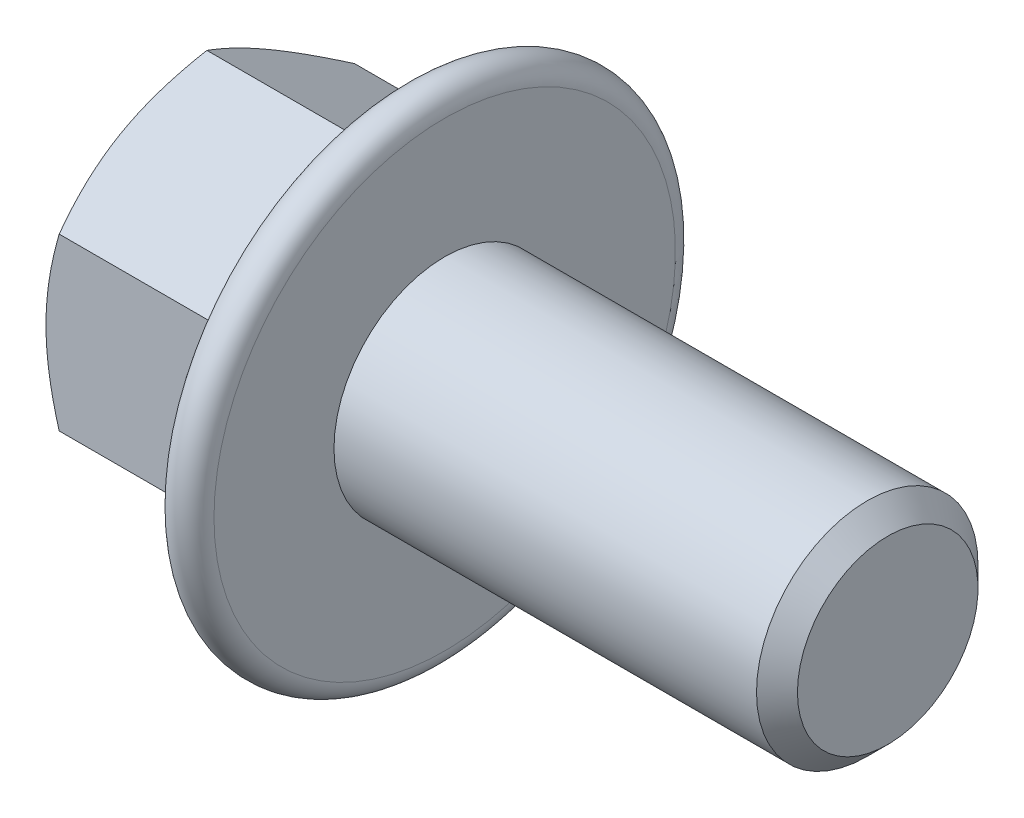
SolidWorks part; units mm, degrees
material "ASTM A36 Steel"
ref_plane "Front Plane" through (0, 0, 0) normal (0, 0, 1) x (1, 0, 0)
ref_plane "Top Plane" through (0, 0, 0) normal (0, 1, 0) x (1, 0, 0)
ref_plane "Right Plane" through (0, 0, 0) normal (1, 0, 0) x (0, 0, -1)
sketch "BaseHeadSke" plane through (0, 0, 0) normal (1, 0, 0) x (0, 0, -1)
  line L1 (0, 4.6188) -> (-4, 2.3094)
  line L2 (-4, 2.3094) -> (-4, -2.3094)
  line L3 (-4, -2.3094) -> (0, -4.6188)
  line L4 (0, -4.6188) -> (4, -2.3094)
  line L5 (4, -2.3094) -> (4, 2.3094)
  line L6 (4, 2.3094) -> (0, 4.6188)
  circle A0 centre (0, 0) radius 4 construction
  dimension "Width_flats" = 8
extrude "BaseHead" add sketch "BaseHeadSke" along normal blind 6.8
sketch "HeadChamferSke" plane through (0, 0, 0) normal (0, 0, 1) x (1, 0, 0)
  line L0 (0, 0) -> (28.0814, 0) construction
  line L1 (0, 2.3094) -> (0, -2.3094) construction
  line L2 (0, 4.6188) -> (0, 4)
  line L3 (0, 4) -> (0.3573, 4.6188)
  line L4 (0.3573, 4.6188) -> (0, 4.6188)
  line L7 (6.8, 4.6188) -> (0, 4.6188) construction
  dimension "Angle_Chamfer_Head" = 30
revolve "HeadChamfer" cut sketch "HeadChamferSke" angle 360 about L0
sketch "BodySke" plane through (0, 0, 0) normal (0, 0, 1) x (1, 0, 0)
  line L0 (0, 0) -> (117.0647, 0) construction
  line L1 (0, 0) -> (0, 3)
  line L2 (0, 3.4641) -> (0, 0) construction
  line L3 (0, 3) -> (18.2455, 3)
  line L4 (18.2455, 3) -> (18.8, 2.4455)
  line L5 (18.8, 2.4455) -> (18.8, 0)
  line L6 (18.8, 0) -> (0, 0)
  line L7 (6.8, 2.3094) -> (6.8, -2.3094) construction
  line L8 (7.8, 0) -> (7.8, 14.6766) construction
  line L9 (6.8, 0) -> (6.8, 14.6766) construction
  dimension "Thread_length" = 12
  dimension "Thread_minor" = 4.891
  dimension "Advance" = 1
revolve "BaseBody" add sketch "BodySke" angle 360 about L0
cosmetic thread "ThreadCosmetic" [suppressed] parameters "Thread_length"=12, "Thread_minor"=4.891
sketch "FlangeSke" plane through (0, 0, 0) normal (0, 0, 1) x (1, 0, 0)
  line L0 (0, 0) -> (112.8691, 0) construction
  line L1 (6.8, 0) -> (6.8, 6.25)
  line L2 (6.8, 0) -> (3.3899, 0)
  line L3 (3.3899, 0) -> (5.7332, 6.4381)
  line L4 (6.8, 4.6188) -> (6.8, 2.3094) construction
  line L5 (5.7, 6.347) -> (5.7, 24.901) construction
  arc A0 (6.8, 6.25) -> (5.7332, 6.4381) centre (6.25, 6.25) ccw
  dimension "Flange_diameter" = 13.6
  dimension "Flange_Angle" = 20
  dimension "Flange_thickness" = 1.1
revolve "Flange" add sketch "FlangeSke" angle 360 about L0
fillet "FlangeHexFillet" radius 0.11 6 edges
fillet "HeadFillet" [suppressed] radius 0.25
sketch "ThdSchSke" plane through (0, 0, 0) normal (0, 0, 1) x (1, 0, 0)
  line L0 (0, 0) -> (114.7993, 0) construction
  line L1 (17.2455, 3.6403) -> (17.2455, 3)
  line L2 (17.2455, 3.6403) -> (17.8858, 3.6403)
  line L3 (17.8858, 3.6403) -> (17.8858, 3)
  line L4 (17.8858, 3) -> (17.5656, 2.4455)
  line L5 (17.5656, 2.4455) -> (17.2455, 3)
  dimension "D1" = 1
revolve "ThreadSchematic" [suppressed] cut sketch "ThdSchSke" angle 360 about L0
pattern_linear "ThdSchPat" [suppressed] of bodies 117
equation "\"Thread_length@ThreadCosmetic\" = \"Thread_length@BodySke\""
equation "\"Thread_minor@ThreadCosmetic\" = \"Thread_minor@BodySke\""
equation "\"D1@ThdSchSke\" = \"Advance@BodySke\""
equation "\"Advance@ThdSchPat\" = \"Advance@BodySke\""
equation "\"Tooth_Num@ThdSchPat\" =  int( \"Thread_length@BodySke\" / \"Advance@BodySke\" ) - 1 "
